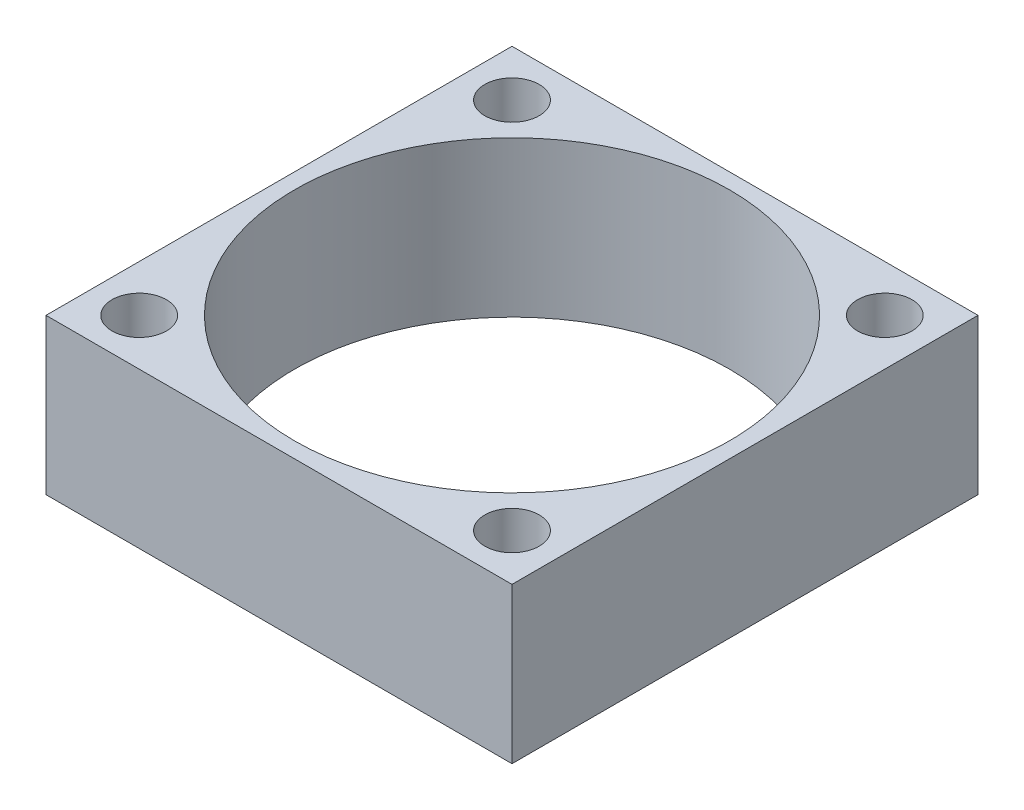
SolidWorks part; units mm, degrees
ref_plane "Спереди" through (0, 0, 0) normal (0, 0, 1) x (1, 0, 0)
ref_plane "Сверху" through (0, 0, 0) normal (0, 1, 0) x (1, 0, 0)
ref_plane "Справа" through (0, 0, 0) normal (1, 0, 0) x (0, 0, -1)
sketch "Эскиз1" plane through (0, 0, 0) normal (0, 1, 0) x (1, 0, 0)
  line L1 (0, 0) -> (30, 0)
  line L2 (0, 0) -> (0, 30)
  line L3 (0, 30) -> (30, 30)
  line L4 (30, 0) -> (30, 30)
  circle A0 centre (15, 15) radius 14
extrude "Бобышка-Вытянуть1" add sketch "Эскиз1" along normal blind 10
hole_wizard "Диаметр отверстия Ø3.5 (3.5)1" positions "Эскиз2" profile "Эскиз3" hole size "Ø3.5" standard "ISO" end condition through all
sketch "Эскиз2" plane through (0, 10, 0) normal (0, 1, 0) x (1, 0, 0)
  line L0 (30, 30) -> (0, 30) construction
  line L1 (0, 30) -> (0, 0) construction
  line L2 (0, 0) -> (30, 0) construction
  line L3 (30, 0) -> (30, 30) construction
  point P0 (3, 27)
  point P2 (27, 27)
  point P4 (27, 3)
  point P6 (3, 3)
  dimension "D1" = 3
  dimension "D2" = 3
  dimension "D3" = 3
  dimension "D4" = 3
  dimension "D5" = 3
  dimension "D6" = 3
  dimension "D7" = 3
  dimension "D8" = 3
sketch "Эскиз3" plane through (3, 10, -27) normal (1, 0, 0) x (0, 0, 1)
  line L0 (0, 0) -> (0, 10)
  line L1 (0, 10) -> (1.75, 10)
  line L2 (1.75, 10) -> (1.75, 0)
  line L5 (1.75, 0) -> (0, 0)
  line L11 (0, -6.35) -> (0, 107.95) construction
  dimension "Диаметр сквозного отверстия" = 3.5
  dimension "Глубина сквозного отверстия" = 10
